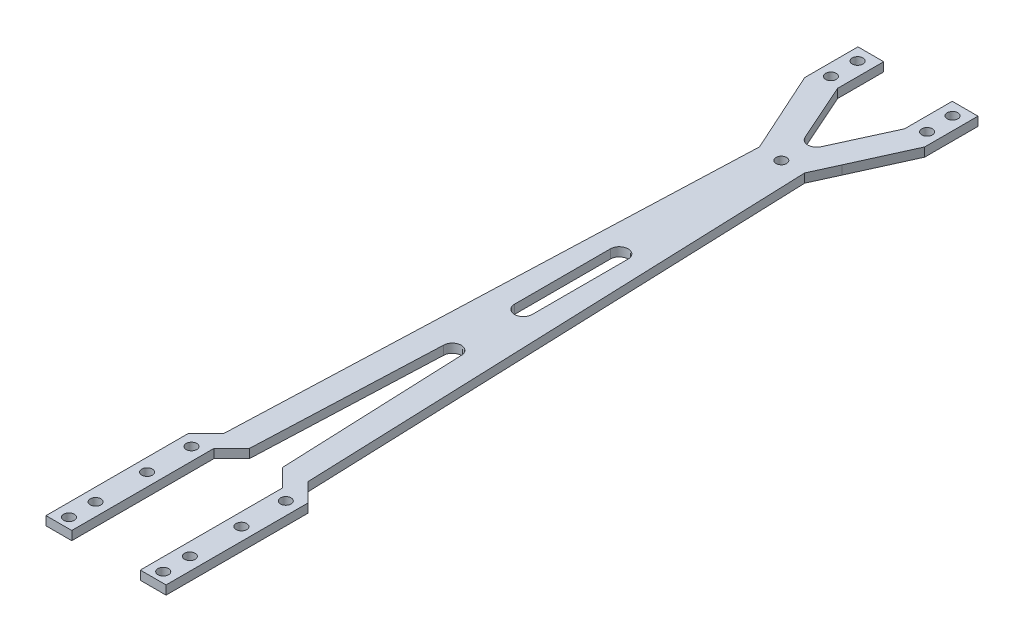
SolidWorks part; units mm, degrees
material "Zoltek Panex 33"
ref_plane "Front Plane" through (0, 0, 0) normal (0, 0, 1) x (1, 0, 0)
ref_plane "Top Plane" through (0, 0, 0) normal (0, 1, 0) x (1, 0, 0)
ref_plane "Right Plane" through (0, 0, 0) normal (1, 0, 0) x (0, 0, -1)
sketch "Sketch1" plane through (0, 0, 0) normal (0, 1, 0) x (1, 0, 0)
  line L0 (34.9366, 74.8642) -> (174.6832, 74.8642) construction
  line L1 (12.4232, 97.6598) -> (60.4232, 97.6598) construction
  line L7 (0, 0) -> (33.8, 0)
  line L8 (0, 0) -> (0, 228.6)
  line L9 (0, 228.6) -> (33.8, 228.6)
  line L10 (33.8, 0) -> (33.8, 228.6)
  dimension "D1" = 228.6
  dimension "D2" = 33.8
extrude "Boss-Extrude1" add sketch "Sketch1" along normal blind 2.5 contours L8 L9 L10 L7
sketch "Sketch2" plane through (0, 2.5, 0) normal (0, 1, 0) x (1, 0, 0)
  line L0 (0, 228.6) -> (7.25, 228.6)
  line L1 (0, 228.6) -> (33.8, 228.6) construction
  line L2 (33.8, 228.6) -> (26.55, 228.6)
  line L3 (0, 0) -> (7.25, 0)
  line L4 (0, 0) -> (33.8, 0) construction
  line L5 (33.8, 0) -> (26.55, 0)
  line L6 (7.25, 228.6) -> (7.25, 215.6)
  line L7 (26.55, 228.6) -> (26.55, 215.1739)
  line L8 (0, 228.6) -> (0, 213.6)
  line L9 (0, 0) -> (0, 228.6) construction
  line L10 (33.8, 228.6) -> (33.8, 213.6)
  line L11 (33.8, 0) -> (33.8, 228.6) construction
  line L12 (7.25, 215.6) -> (14.5825, 199.1624)
  line L13 (0, 213.6) -> (7.2352, 197.6328)
  line L14 (33.8, 213.6) -> (26.55, 197.6)
  line L15 (26.55, 215.1739) -> (19.2175, 199.1624)
  line L16 (55.9315, 179.477) -> (103.9315, 179.477) construction
  line L17 (0, 40) -> (5, 45)
  line L20 (7.2352, 197.6328) -> (10.5352, 190.35)
  line L21 (5, 45) -> (10.5352, 190.35)
  line L22 (28.5888, 45.2112) -> (23.25, 190.35)
  line L23 (0, 40) -> (0, 0)
  line L24 (33.8, 40) -> (33.8, 0)
  line L25 (26.55, 0) -> (26.55, 40)
  line L26 (7.25, 0) -> (7.25, 40)
  line L27 (7.25, 40) -> (12.25, 45)
  line L28 (26.55, 40) -> (21.55, 45)
  line L29 (14.4, 97.5) -> (12.25, 45)
  line L30 (19.4, 97.5) -> (21.55, 45)
  line L31 (33.8, 40) -> (28.5888, 45.2112)
  line L36 (26.55, 197.6) -> (23.25, 190.35)
  line L37 (14.4, 144.5) -> (14.4, 117.5)
  line L38 (19.4, 144.5) -> (19.4, 117.5)
  spline S0 degree 3 poles (14.5825, 199.1624) (14.7116, 198.8421) (15.0238, 198.3786) (15.615, 197.9288) (16.2519, 197.647) (17.0234, 197.5532) (17.8598, 197.743) (18.6719, 198.2407) (19.0708, 198.798) (19.2175, 199.1624) knots 0 0 0 0 0.175078 0.27695 0.373163 0.525808 0.66207 0.801161 1 1 1 1
  spline S1 degree 3 poles (14.4, 97.5) (14.3996, 97.8087) (14.485, 98.2611) (14.7534, 98.8073) (15.0541, 99.2151) (15.5867, 99.682) (16.3803, 100.0073) (17.2083, 100.0151) (17.858, 99.8334) (18.395, 99.5372) (18.8503, 99.1065) (19.2726, 98.4335) (19.4007, 97.868) (19.4, 97.5) knots 0 0 0 0 0.118087 0.173139 0.232058 0.311091 0.441944 0.550747 0.622172 0.698429 0.783498 0.859367 1 1 1 1
  spline S2 degree 3 poles (14.4, 117.5) (14.3994, 117.1322) (14.5368, 116.5242) (14.9916, 115.8396) (15.5867, 115.3182) (16.4416, 114.9669) (17.4395, 114.9971) (18.3302, 115.3815) (19.1433, 116.173) (19.4016, 116.9977) (19.4, 117.5) knots 0 0 0 0 0.141327 0.232053 0.311236 0.442338 0.576356 0.682961 0.808346 1 1 1 1
  spline S3 degree 3 poles (14.4, 144.5) (14.3953, 145.2238) (14.9914, 146.5127) (16.6261, 147.1076) (17.9036, 146.8721) (19.0225, 146.1036) (19.4035, 145.0984) (19.4, 144.5) knots 0 0 0 0 0.276967 0.498349 0.612919 0.769853 1 1 1 1
  dimension "D1" = 7.25
  dimension "D2" = 7.25
extrude "Cut-Extrude1" cut sketch "Sketch2" against normal blind 2.5 contours L38 S2 L37 S3
extrude "Cut-Extrude2" cut sketch "Sketch2<6>" against normal blind 2.5 flip side to cut contours L14 L36 L22 L31 L24 L5 L25 L28 L30 S1 L29 L27 L26 L3 L23 L17 L21 L20 L13 L8 L0 L6 L12 S0 L15 L7 L2 L10
sketch "Sketch2<6>" plane through (0, 2.5, 0) normal (0, 1, 0) x (1, 0, 0) same geometry as "Sketch2"
sketch "Sketch5" plane through (0, 2.5, 0) normal (0, 1, 0) x (1, 0, 0)
  line L0 (0, 228.6) -> (7.25, 228.6) construction
  line L1 (33.8, 228.6) -> (26.55, 228.6) construction
  line L2 (7.25, 0) -> (7.25, 40) construction
  line L3 (33.8, 40) -> (33.8, 0) construction
  circle A0 centre (3.3984, 225.1) radius 1.5
  circle A1 centre (3.3984, 217.6) radius 1.5
  circle A2 centre (30.1328, 225.1) radius 1.5
  circle A3 centre (30.4682, 217.6) radius 1.5
  circle A4 centre (3.625, 2.8331) radius 1.5
  circle A6 centre (30.175, 2.8331) radius 1.5
  circle A12 centre (3.625, 10.3331) radius 1.5
  circle A13 centre (3.625, 24.8331) radius 1.5
  circle A14 centre (3.625, 37.3331) radius 1.5
  circle A18 centre (30.175, 10.3331) radius 1.5
  circle A19 centre (30.175, 24.8331) radius 1.5
  circle A20 centre (30.175, 37.3331) radius 1.5
  circle A21 centre (16.9266, 190.1) radius 1.5
  dimension "D5" = 3.625
  dimension "D7" = 7.5
  dimension "D1" = 3.5
  dimension "D2" = 3.5
  dimension "D3" = 7.5
  dimension "D4" = 7.5
  dimension "D6" = 3.625
  dimension "D8" = 7.5
  dimension "D9" = 14.5
  dimension "D10" = 14.5
  dimension "D11" = 12.5
  dimension "D12" = 12.5
extrude "Cut-Extrude3" cut sketch "Sketch5" against normal blind 2.5 contours A0 | A2 | A3 | A1 | A14 | A20 | A19 | A13 | A12 | A4 | A6 | A18 | A21 | A3 region at (3.3984, 2.5, -225.1) region at (3.3984, 2.5, -217.6) region at (30.1328, 2.5, -225.1) region at (30.4682, 2.5, -217.6) region at (3.625, 2.5, -2.8331) region at (30.175, 2.5, -2.8331) region at (3.625, 2.5, -10.3331) region at (3.625, 2.5, -24.8331) region at (3.625, 2.5, -37.3331) region at (30.175, 2.5, -10.3331) region at (30.175, 2.5, -24.8331) region at (30.175, 2.5, -37.3331)
